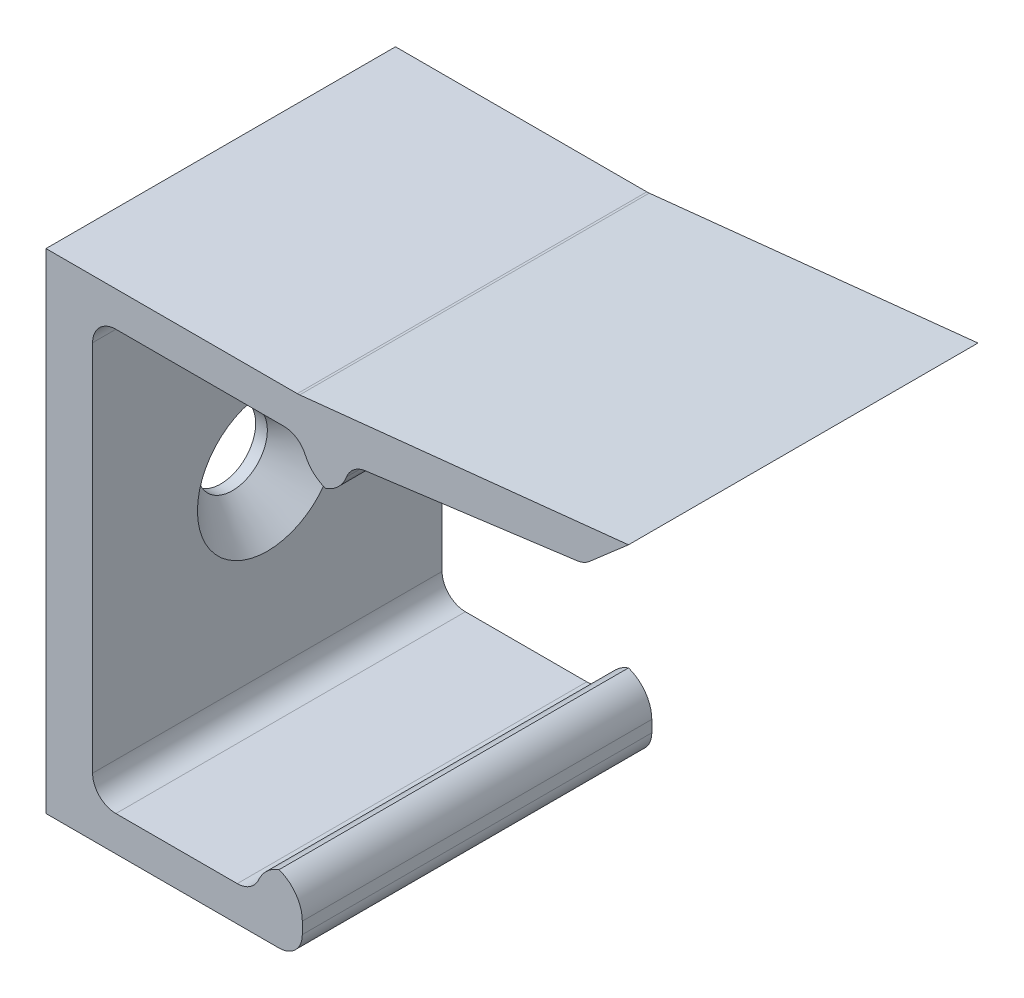
SolidWorks part; units mm, degrees
ref_plane "Front Plane" through (0, 0, 0) normal (0, 0, 1) x (1, 0, 0)
ref_plane "Top Plane" through (0, 0, 0) normal (0, 1, 0) x (1, 0, 0)
ref_plane "Right Plane" through (0, 0, 0) normal (1, 0, 0) x (0, 0, -1)
sketch "Sketch1" plane through (0, 0, 0) normal (0, 0, 1) x (1, 0, 0)
  line L0 (0, 0) -> (11, 0)
  line L1 (11, 0) -> (11, 3)
  line L2 (11, 3) -> (9, 3)
  line L3 (9, 3) -> (9, 1.5)
  line L4 (9, 1.5) -> (2, 1.5)
  line L5 (2, 1.5) -> (2, 19.5)
  line L6 (2, 19.5) -> (11, 19.5)
  line L7 (11, 19.5) -> (11, 18)
  line L8 (11, 18) -> (13, 18)
  line L11 (0, 21) -> (0, 0)
  line L13 (23.0949, 20.8324) -> (25, 22.4885)
  line L14 (13, 19.5) -> (23.0949, 20.8324)
  line L15 (13, 18) -> (13, 19.5)
  line L16 (0, 21) -> (10.8378, 21)
  line L17 (10.8378, 21) -> (25, 22.4885)
  dimension "D1" = 2
  dimension "D2" = 2
  dimension "D3" = 7
  dimension "D4" = 1.5
  dimension "D5" = 2
  dimension "D6" = 35
  dimension "D7" = 9
  dimension "D8" = 18
  dimension "D9" = 3
  dimension "D10" = 1.5
  dimension "D11" = 0
  dimension "D12" = 6
  dimension "D13" = 25
  dimension "D14" = 3
extrude "Boss-Extrude1" add sketch "Sketch1" along normal blind 15 contours L6 L7 L8 L15 L14 L13 L17 L16 L11 L0 L1 L2 L3 L4 L5
sketch "Sketch2" plane through (2, 0, 0) normal (1, 0, 0) x (0, 0, -1)
  line L0 (0, 1.5) -> (0, 19.5) construction
  circle A0 centre (-7.5, 10) radius 1.5
  dimension "D1" = 7.5
  dimension "D3" = 3
  dimension "D2" = 8.5
extrude "Cut-Extrude1" cut sketch "Sketch2" against normal through all both and the other way through all
chamfer "Chamfer1" distance 1.5 angle 45 1 edges at (2, 8.5, 7.5)
fillet "Fillet1" radius 1.5 4 edges at (9, 3, 7.5) (11, 3, 7.5) (13, 18, 7.5) (11, 18, 7.5)
fillet "Fillet2" radius 1 5 edges at (11, 0, 7.5) (2, 1.5, 7.5) (2, 19.5, 7.5) (23.0949, 20.8324, 7.5) (10.8378, 21, 7.5)
fillet "Fillet3" radius 1 3 edges at (11, 19.5, 7.5) (9, 1.5, 7.5) (13, 19.5, 7.5)
